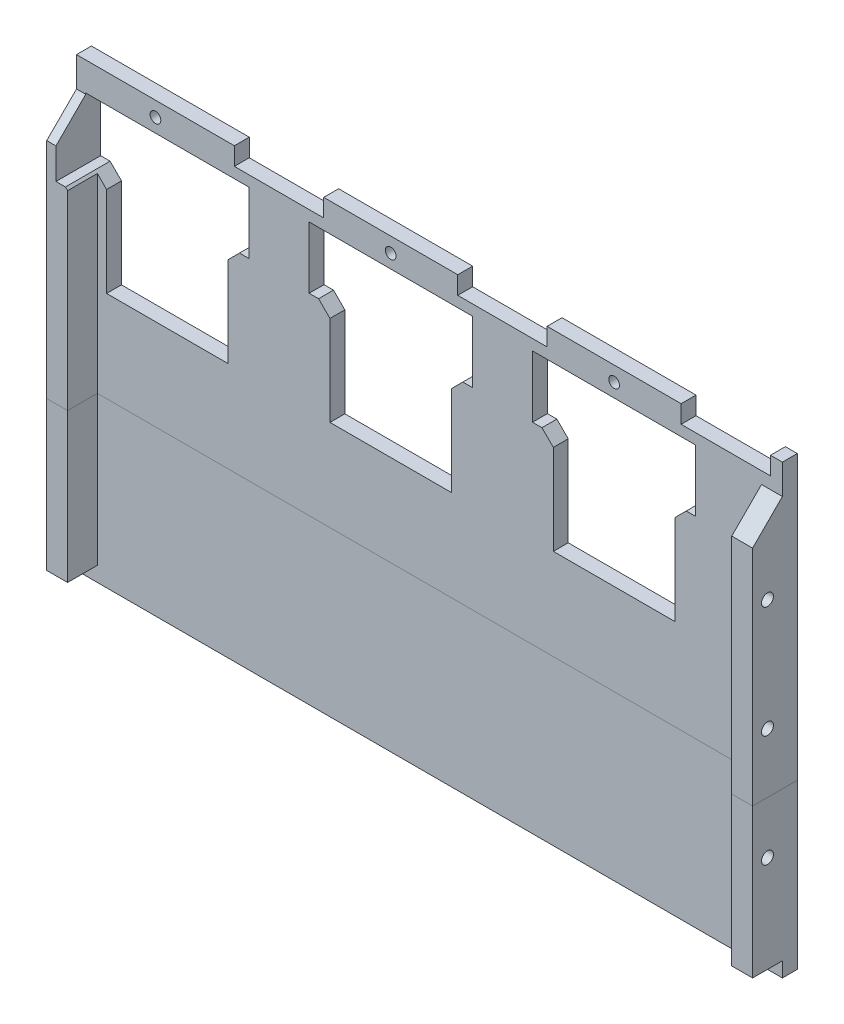
SolidWorks part; units mm, degrees
ref_plane "Płaszczyzna przednia" through (0, 0, 0) normal (0, 0, 1) x (1, 0, 0)
ref_plane "Płaszczyzna górna" through (0, 0, 0) normal (0, 1, 0) x (1, 0, 0)
ref_plane "Płaszczyzna prawa" through (0, 0, 0) normal (1, 0, 0) x (0, 0, -1)
sketch "Szkic1" plane through (0, 0, 0) normal (0, 0, 1) x (1, 0, 0)
  line L1 (-118.5, -75) -> (118.5, -75)
  line L2 (-118.5, -75) -> (-118.5, 75)
  line L3 (-118.5, 75) -> (118.5, 75)
  line L4 (118.5, -75) -> (118.5, 75)
  line L5 (0, 75) -> (0, -75) construction
  line L6 (-118.5, 0) -> (118.5, 0) construction
  point P0 (0, 0)
  dimension "D1" = 237
  dimension "D2" = 150
extrude "Dodanie-wyciągnięcie1" add sketch "Szkic1" along normal blind 5
sketch "Szkic2" plane through (0, 0, 5) normal (0, 0, 1) x (1, 0, 0)
  line L0 (118.5, -75) -> (118.5, 75) construction
  line L1 (118.5, 65) -> (111.5, 65)
  line L2 (118.5, 65) -> (118.5, -70)
  line L3 (118.5, -70) -> (111.5, -70)
  line L4 (111.5, 65) -> (111.5, -70)
  line L5 (115, -70) -> (115, 65) construction
  line L6 (118.5, -2.5) -> (111.5, -2.5) construction
  line L7 (118.5, 75) -> (-118.5, 75) construction
  line L8 (-118.5, -75) -> (118.5, -75) construction
  line L9 (0, 0) -> (0, 75) construction
  line L10 (-118.5, -2.5) -> (-111.5, -2.5) construction
  line L11 (-115, -70) -> (-115, 65) construction
  line L12 (-111.5, 65) -> (-111.5, -70)
  line L13 (-118.5, -70) -> (-111.5, -70)
  line L14 (-118.5, 65) -> (-118.5, -70)
  line L15 (-118.5, 65) -> (-111.5, 65)
  point P20 (-115, -2.5)
  point P300 (115, -2.5)
  dimension "D1" = 10
  dimension "D2" = 5
  dimension "D3" = 7
extrude "Dodanie-wyciągnięcie2" add sketch "Szkic2" along normal blind 10
sketch "Szkic3" plane through (118.5, 0, 0) normal (1, 0, 0) x (0, 0, -1)
  line L0 (-10, 65) -> (-10, -70) construction
  line L1 (-15, 65) -> (-5, 65) construction
  line L2 (-15, -70) -> (-5, -70) construction
  line L3 (0, 0) -> (-15, 0) construction
  line L4 (0, -75) -> (0, 75) construction
  line L5 (-15, -70) -> (-15, 65) construction
  point P6 (-10, 37.5)
  point P7 (-10, 0)
  point P8 (-10, -37.5)
  dimension "D1" = 37.5
hole_wizard "Otwór Ø4.0 (4)1" positions "Szkic3" profile "Szkic4" hole size "Ø4.0" standard "DIN"
sketch "Szkic4" plane through (118.5, -37.5, 10) normal (0, 1, 0) x (0, 0, -1)
  line L0 (0, 0) -> (0, 6.7)
  line L1 (0, 6.7) -> (2, 6.7)
  line L2 (2, 6.7) -> (2, 0)
  line L5 (2, 0) -> (0, 0)
  line L10 (0, 6.7) -> (-2, 6.7) construction
  line L11 (0, -6.35) -> (0, 107.95) construction
  dimension "Średnica otworu" = 4
  dimension "Głębokość otworu" = 6.7
  dimension "Kąt wiertła" = 180
ref_plane "Płaszczyzna1" through (0, 0, 0) normal (-1, 0, 0) x (0, 0, 1)
mirror "Lustro1" about plane through (0, 0, 0) normal (-1, 0, 0) of "Otwór Ø4.0 (4)1"
chamfer "Sfazowanie1" distance 10 angle 45 2 edges at (-115, 65, 15) (115, 65, 15)
sketch "Szkic5" plane through (0, 0, 0) normal (0, 0, -1) x (-1, 0, 0)
  line L0 (-86, 45.0546) -> (-86, 45)
  line L2 (112, 45) -> (112, 51) construction
  line L3 (-89, 65.4) -> (-89, 69)
  line L5 (-35, 65.4) -> (-35, 69)
  line L8 (-14, 65.4) -> (-14, 69)
  line L9 (40, 65.4) -> (40, 69)
  line L10 (61, 65.4) -> (61, 69)
  line L11 (115, 65.4) -> (115, 75)
  line L12 (-118.5, 75) -> (118.5, 75) construction
  line L13 (115, 75) -> (65.5, 75)
  line L14 (35.5, 75) -> (-9.5, 75)
  line L17 (-37.7797, 44.6546) -> (-34.6, 44.6546)
  line L20 (-39.5, 75) -> (-84.5, 75)
  line L21 (-82.4, 10.6) -> (-41.6, 10.6)
  line L23 (-41.6, 10.6) -> (-41.6, 40.8343)
  line L24 (-41.6, 40.8343) -> (-38.7172, 43.7172)
  line L25 (-38.7172, 43.7172) -> (-37.7797, 44.6546)
  line L26 (-37.7797, 44.6546) -> (-37.7797, 44.6546)
  line L27 (-37.7797, 44.6546) -> (-34.6, 44.6546)
  line L29 (-34.6, 44.6546) -> (-34.6, 65)
  line L30 (-34.6, 65) -> (-34.6, 68.6)
  line L31 (-34.6, 68.6) -> (-14.4, 68.6)
  line L32 (-14.4, 65) -> (-14.4, 68.6)
  line L33 (-14.4, 65) -> (-14.4, 44.6546)
  line L35 (-14.4, 44.6546) -> (-11.2203, 44.6546)
  line L37 (-11.2203, 44.6546) -> (-11.2203, 44.6546)
  line L38 (-11.2203, 44.6546) -> (-10.2828, 43.7172)
  line L42 (-10.2828, 43.7172) -> (-7.4, 40.8343)
  line L44 (37, 45) -> (37, 51) construction
  line L45 (-7.4, 40.8343) -> (-7.4, 10.6)
  line L47 (-7.4, 10.6) -> (33.4, 10.6)
  line L50 (33.4, 10.6) -> (33.4, 40.8343)
  line L51 (33.4, 40.8343) -> (36.2828, 43.7172)
  line L52 (36.2828, 43.7172) -> (37.2203, 44.6546)
  line L53 (37.2203, 44.6546) -> (37.2203, 44.6546)
  line L54 (37.2203, 44.6546) -> (40.4, 44.6546)
  line L55 (40.4, 44.6546) -> (40.4, 65)
  line L56 (40.4, 65) -> (40.4, 68.6)
  line L59 (-34.6, 44.6546) -> (-34.6, 65.4)
  line L61 (40.4, 68.6) -> (60.6, 68.6)
  line L62 (60.6, 65) -> (60.6, 68.6)
  line L63 (60.6, 65) -> (60.6, 44.6546)
  line L65 (60.6, 44.6546) -> (63.7797, 44.6546)
  line L66 (63.7797, 44.6546) -> (63.7797, 44.6546)
  line L67 (63.7797, 44.6546) -> (64.7172, 43.7172)
  line L68 (64.7172, 43.7172) -> (67.6, 40.8343)
  line L69 (67.6, 40.8343) -> (67.6, 10.6)
  line L70 (67.6, 10.6) -> (108.4, 10.6)
  line L71 (108.4, 10.6) -> (108.4, 40.8343)
  line L72 (108.4, 40.8343) -> (111.2828, 43.7172)
  line L73 (111.2828, 43.7172) -> (112.2203, 44.6546)
  line L74 (112.2203, 44.6546) -> (112.2203, 44.6546)
  line L75 (112.2203, 44.6546) -> (115.4, 44.6546)
  line L76 (115.4, 44.6546) -> (115.4, 65)
  line L77 (115.4, 65) -> (115.4, 75.4)
  line L78 (115.4, 75.4) -> (65.5, 75.4)
  line L79 (65.5, 75.4) -> (35.5, 75.4)
  line L80 (35.5, 75.4) -> (-9.5, 75.4)
  line L84 (-9.5, 75.4) -> (-39.5, 75.4)
  line L87 (-39.5, 75.4) -> (-84.5, 75.4)
  line L89 (-84.5, 75.4) -> (-114.9, 75.4)
  line L91 (-114.9, 75.4) -> (-114.9, 68.6)
  line L92 (-114.9, 68.6) -> (-89.4, 68.6)
  line L93 (-89.4, 65) -> (-89.4, 68.6)
  line L95 (-89.4, 65) -> (-89.4, 44.6546)
  line L96 (-89.4, 44.6546) -> (-86.2203, 44.6546)
  line L97 (-86.2203, 44.6546) -> (-86.2203, 44.6546)
  line L98 (-86.2203, 44.6546) -> (-85.2828, 43.7172)
  line L99 (-85.2828, 43.7172) -> (-82.4, 40.8343)
  line L100 (-82.4, 40.8343) -> (-82.4, 10.6)
  line L102 (-34.6, 65.4) -> (-89.4, 65.4)
  line L103 (-89.4, 65.4) -> (-89.4, 44.6546)
  line L104 (-89.4, 44.6546) -> (-86.2203, 44.6546)
  line L105 (37, 44.6546) -> (40.4, 44.6546)
  line L106 (-114.5, 93) -> (-114.5, 69)
  line L107 (-114.5, 69) -> (-84.5, 69)
  line L109 (-84.5, 69) -> (-84.5, 93)
  line L110 (-84.5, 93) -> (-114.5, 93)
  line L117 (-114.5, 75.4) -> (-114.5, 69)
  line L118 (-114.5, 69) -> (-84.5, 69)
  line L119 (-84.5, 69) -> (-84.5, 75.4)
  line L121 (-9.5, 93) -> (-39.5, 93)
  line L122 (-39.5, 93) -> (-39.5, 69)
  line L125 (-39.5, 69) -> (-9.5, 69)
  line L126 (-84.5, 75) -> (-114.5, 75)
  line L127 (40.4, 44.6546) -> (40.4, 65.4)
  line L128 (35.5, 69) -> (65.5, 69) construction
  line L129 (40.4, 65.4) -> (-14.4, 65.4)
  line L131 (-9.5, 69) -> (-9.5, 93)
  line L132 (-39.5, 69) -> (-9.5, 69) construction
  line L133 (-14.4, 65.4) -> (-14.4, 44.6546)
  line L134 (-114.5, 93) -> (-114.5, 69) construction
  line L135 (-114.5, 69) -> (-84.5, 69) construction
  line L137 (-9.5, 75) -> (-39.5, 75)
  line L140 (112, 45) -> (112, 45.0546)
  line L141 (-39.5, 75.4) -> (-39.5, 69)
  line L159 (-39.5, 69) -> (-9.5, 69)
  line L163 (-9.5, 69) -> (-9.5, 75.4)
  line L164 (65.5, 93) -> (35.5, 93)
  line L165 (35.5, 93) -> (35.5, 69)
  line L167 (35.5, 69) -> (65.5, 69)
  line L168 (65.5, 69) -> (65.5, 93)
  line L170 (35.5, 75.4) -> (35.5, 69)
  line L171 (35.5, 69) -> (65.5, 69)
  line L173 (65.5, 69) -> (65.5, 75.4)
  line L175 (-14.4, 44.6546) -> (-11.2203, 44.6546)
  line L182 (37, 45) -> (37, 45.0546)
  line L183 (112, 44.6546) -> (115.4, 44.6546)
  line L200 (115.4, 44.6546) -> (115.4, 65.4)
  line L201 (115.4, 65.4) -> (60.6, 65.4)
  line L205 (60.6, 65.4) -> (60.6, 44.6546)
  line L206 (60.6, 44.6546) -> (63.7797, 44.6546)
  line L207 (-89, 65) -> (-89, 69) construction
  line L208 (-35, 65) -> (-35, 69) construction
  line L209 (61, 65) -> (61, 69) construction
  line L210 (-14, 65) -> (-14, 69) construction
  line L212 (40, 65) -> (40, 69) construction
  line L213 (115, 65) -> (115, 75) construction
  line L266 (40, 69) -> (61, 69)
  line L270 (-35, 69) -> (-14, 69)
  line L272 (-114.5, 75) -> (-114.5, 69)
  line L273 (-114.5, 69) -> (-89, 69)
  line L280 (-118.5, 75) -> (-118.5, -75)
  line L281 (-118.5, -75) -> (118.5, -75)
  line L282 (118.5, -75) -> (118.5, 75)
  line L283 (118.5, 75) -> (-118.5, 75)
  line L287 (65.5, 75) -> (35.5, 75)
  line L334 (-89, 45.0546) -> (-86, 45.0546) construction
  line L336 (-86, 45) -> (-85, 44) construction
  line L337 (-85, 44) -> (-82, 41) construction
  line L339 (-89, 65) -> (-89, 45.0546) construction
  line L341 (-35, 45.0546) -> (-35, 65) construction
  line L343 (-38, 45.0546) -> (-35, 45.0546) construction
  line L344 (-42, 41) -> (-39, 44) construction
  line L345 (-39, 44) -> (-38, 45) construction
  line L346 (-82, 41) -> (-82, 11) construction
  line L347 (-82, 11) -> (-42, 11) construction
  line L348 (-42, 11) -> (-42, 41) construction
  line L350 (-38, 45) -> (-38, 45.0546) construction
  line L352 (-7, 41) -> (-7, 11) construction
  line L353 (-10, 44) -> (-7, 41) construction
  line L354 (-11, 45) -> (-10, 44) construction
  line L355 (-14, 45.0546) -> (-11, 45.0546) construction
  line L357 (-11, 45.0546) -> (-11, 45) construction
  line L358 (-14, 65) -> (-14, 45.0546) construction
  line L361 (40, 45.0546) -> (40, 65) construction
  line L363 (37, 45.0546) -> (40, 45.0546) construction
  line L365 (36, 44) -> (37, 45) construction
  line L366 (33, 41) -> (36, 44) construction
  line L367 (33, 11) -> (33, 41) construction
  line L368 (-7, 11) -> (33, 11) construction
  line L370 (61, 65) -> (61, 45.0546) construction
  line L372 (61, 45.0546) -> (64, 45.0546) construction
  line L374 (65, 44) -> (68, 41) construction
  line L375 (68, 41) -> (68, 11) construction
  line L376 (64, 45) -> (65, 44) construction
  line L377 (64, 45.0546) -> (64, 45) construction
  line L378 (115, 45.0546) -> (115, 65) construction
  line L380 (112, 45.0546) -> (115, 45.0546) construction
  line L382 (111, 44) -> (112, 45) construction
  line L383 (108, 41) -> (111, 44) construction
  line L384 (108, 11) -> (108, 41) construction
  line L385 (68, 11) -> (108, 11) construction
  line M8 (118.5, 75) -> (-118.5, 75)
  dimension "D1" = 0
  dimension "D2" = 0.4
  dimension "D3" = 0
  dimension "D4" = 0
  dimension "D5" = 0
extrude "Wytnij-wyciągnięcie1" cut sketch "Szkic5" against normal up to next contours L30 L102 L93 L95 L96 L98 L99 L100 L21 L23 L24 L25 L17 L29 | L56 L129 L32 L33 L35 L38 L42 L45 L47 L50 L51 L52 L54 L55 | L77 L201 L62 L63 L65 L67 L68 L69 L70 L71 L72 L73 L75 L76 | L118 L119 L117 M8 | L159 L163 L141 M8 | L171 L173 L170 M8 region at (62, 39.9772, 0) region at (99.5, 72, 0) region at (24.5, 72, 0) region at (-13, 39.9772, 0) region at (-50.5, 72, 0) region at (-88, 39.9772, 0)
ref_plane "Płaszczyzna2" through (0, -20, 0) normal (0, -1, 0) x (-1, 0, 0)
split "Podziel1" trim tools "Płaszczyzna2" bodies to split 106 resulting bodies 107 108
sketch "Szkic6" plane through (0, 0, 0) normal (0, 0, -1) x (-1, 0, 0)
  line L0 (-84.5, 75) -> (-39.5, 75) construction
  line L1 (-9.5, 75) -> (35.5, 75) construction
  line L2 (65.5, 75) -> (118.5, 75) construction
  point P0 (-62, 70)
  point P1 (13, 70)
  point P2 (92, 70)
  point P3 (0, 0)
  point P6 (-62, 75)
  point P7 (0, 0)
  point P10 (13, 75)
  point P13 (92, 75)
  point P14 (0, 0)
  dimension "D1" = 5
hole_wizard "Pogłębienie walcowe pod M3 Śrubę z łbem stożkowym ściętym1" positions "Szkic6" profile "Szkic7" counterbore size "M3" standard "DIN"
sketch "Szkic7" plane through (62, 70, 0) normal (1, 0, 0) x (0, 1, 0)
  line L0 (0, 0) -> (0, 7.7815)
  line L1 (0, 7.7815) -> (1.8, 6.7)
  line L2 (1.8, 6.7) -> (1.8, 2.4)
  line L3 (1.8, 2.4) -> (3.5, 2.4)
  line L4 (3.5, 2.4) -> (3.5, 0)
  line L5 (3.5, 0) -> (0, 0)
  line L10 (0, 7.7815) -> (-1.8, 6.7) construction
  line L11 (0, -6.35) -> (0, 107.95) construction
  dimension "Średnica otworu" = 3.6
  dimension "Głębokość otworu" = 6.7
  dimension "Średnica pogłębienia walcowego" = 7
  dimension "Głębokość pogłębienia walcowego" = 2.4
  dimension "Kąt wiertła" = 118
